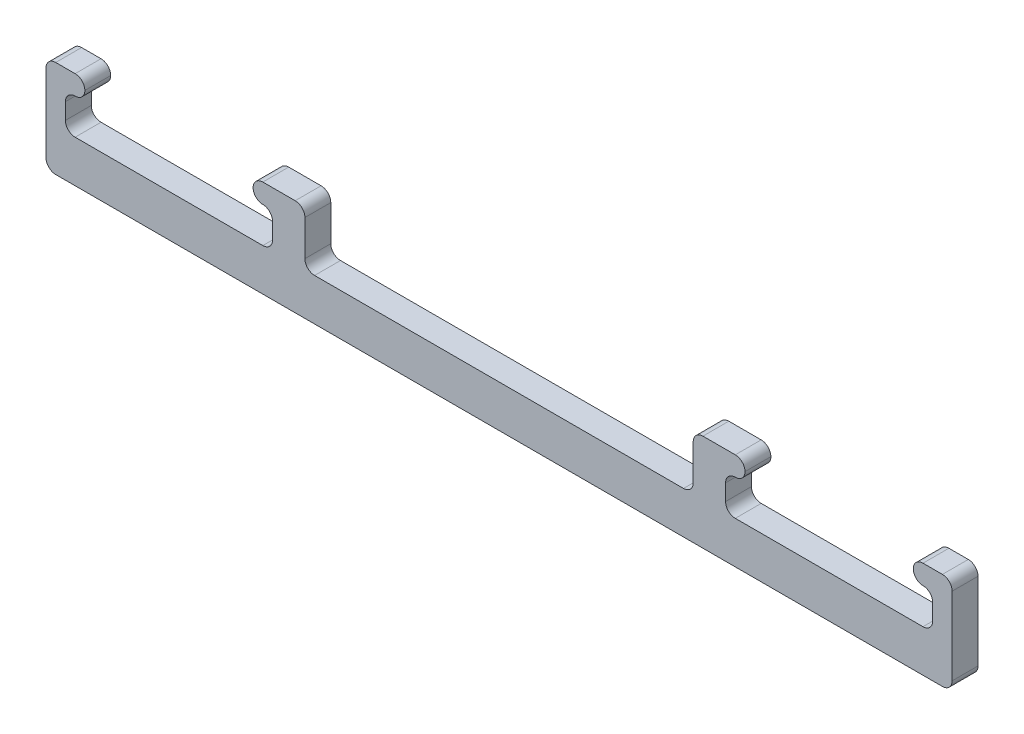
SolidWorks part; units mm, degrees
ref_plane "Plan de face" through (0, 0, 0) normal (0, 0, 1) x (1, 0, 0)
ref_plane "Plan de dessus" through (0, 0, 0) normal (0, 1, 0) x (1, 0, 0)
ref_plane "Plan de droite" through (0, 0, 0) normal (1, 0, 0) x (0, 0, -1)
sketch "Esquisse1" plane through (0, 0, 0) normal (0, 0, 1) x (1, 0, 0)
  line L1 (-70, 0) -> (-70, 15)
  line L13 (-70, 15) -> (70, 15)
  line L14 (70, 15) -> (70, 0)
  line L15 (70, 0) -> (-70, 0)
  dimension "D1" = 15
  dimension "D2" = 140
extrude "Boss.-Extru.1" add sketch "Esquisse1" along normal blind 4
sketch "Esquisse2" plane through (0, 0, 4) normal (0, 0, 1) x (1, 0, 0)
  line L0 (-64, 15) -> (-64, 12)
  line L1 (70, 15) -> (-70, 15) construction
  line L2 (-64, 12) -> (-67, 12)
  line L3 (-67, 12) -> (-67, 6.5)
  line L4 (-67, 6.5) -> (-35, 6.5)
  line L5 (-35, 6.5) -> (-35, 12)
  line L6 (-35, 12) -> (-38, 12)
  line L7 (-38, 12) -> (-38, 15)
  line L8 (-38, 15) -> (-64, 15)
  line L9 (-70, 15) -> (-70, 0) construction
  line L10 (0, 31.8472) -> (0, -32.3214) construction
  line L11 (38, 12) -> (38, 15)
  line L12 (35, 12) -> (38, 12)
  line L13 (35, 6.5) -> (35, 12)
  line L14 (67, 6.5) -> (35, 6.5)
  line L15 (67, 12) -> (67, 6.5)
  line L16 (64, 12) -> (67, 12)
  line L17 (64, 15) -> (64, 12)
  line L18 (38, 15) -> (64, 15)
  point P13 (-36.5, 12)
  point P15 (-38, 13.5)
  point P17 (38, 13.5)
  point P20 (36.5, 12)
  dimension "D1" = 3
  dimension "D2" = 3
  dimension "D3" = 6
  dimension "D4" = 32
  dimension "D5" = 5.5
  dimension "D6" = 3
  dimension "D7" = 3
extrude "Enlèv. mat.-Extru.1" cut sketch "Esquisse2" against normal blind 10
sketch "Esquisse3" plane through (0, 0, 4) normal (0, 0, 1) x (1, 0, 0)
  line L0 (-35, 6.5) -> (-35, 12) construction
  line L1 (-30, 15) -> (30, 15)
  line L2 (-30, 15) -> (-30, 6.5)
  line L3 (-30, 6.5) -> (30, 6.5)
  line L4 (30, 15) -> (30, 6.5)
  line L5 (35, 12) -> (35, 6.5) construction
  line L7 (38, 15) -> (-38, 15) construction
  line L8 (-67, 6.5) -> (-35, 6.5) construction
  dimension "D1" = 5
  dimension "D2" = 5
extrude "Enlèv. mat.-Extru.2" cut sketch "Esquisse3" against normal blind 10
fillet "Congé1" radius 1.5 24 edges at (30, 15, 2) (38, 15, 2) (64, 15, 2) (70, 15, 2) (-70, 0, 2) (-70, 15, 2) (-64, 15, 2) (-64, 12, 2) (-67, 12, 2) (-67, 6.5, 2) (-35, 6.5, 2) (-35, 12, 2) (-38, 12, 2) (-38, 15, 2) (-30, 15, 2) (-30, 6.5, 2) (30, 6.5, 2) (35, 6.5, 2) (67, 6.5, 2) (70, 0, 2) (64, 12, 2) (67, 12, 2) (35, 12, 2) (38, 12, 2)
